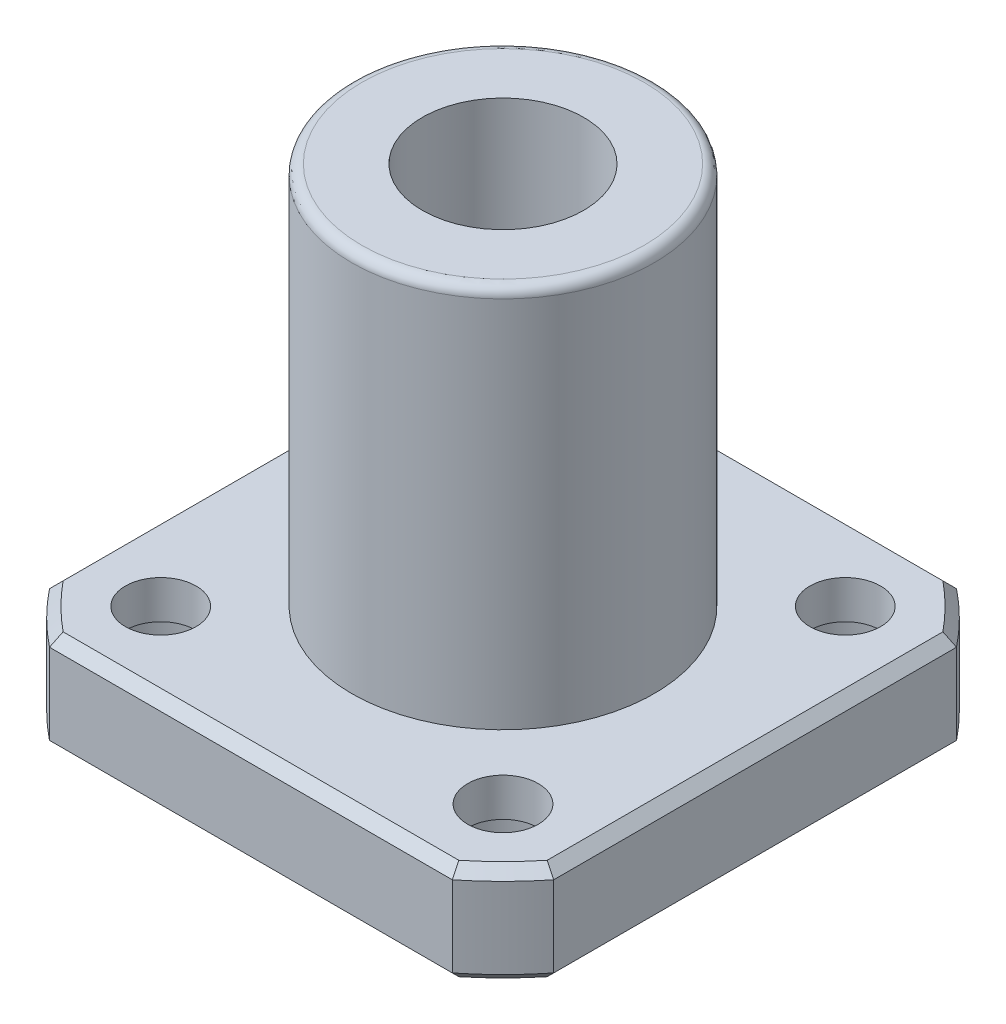
SolidWorks part; units mm, degrees
ref_plane "前视基准面" through (0, 0, 0) normal (0, 0, 1) x (1, 0, 0)
ref_plane "上视基准面" through (0, 0, 0) normal (0, 1, 0) x (1, 0, 0)
ref_plane "右视基准面" through (0, 0, 0) normal (1, 0, 0) x (0, 0, -1)
sketch "草图1" plane through (0, 0, 0) normal (0, 1, 0) x (1, 0, 0)
  line L1 (-12.5, -12.5) -> (12.5, -12.5)
  line L2 (-12.5, -12.5) -> (-12.5, 12.5)
  line L3 (-12.5, 12.5) -> (12.5, 12.5)
  line L4 (12.5, -12.5) -> (12.5, 12.5)
  line L5 (-12.5, -12.5) -> (12.5, 12.5) construction
  line L6 (-12.5, 12.5) -> (12.5, -12.5) construction
  circle A0 centre (0, 0) radius 4
  circle A1 centre (0, 0) radius 7.5
  circle A2 centre (0, 0) radius 16
  circle A3 centre (0, 0) radius 12 construction
  circle A4 centre (-8.4853, 8.4853) radius 1.75
  circle A5 centre (8.4853, 8.4853) radius 1.75
  circle A6 centre (8.4853, -8.4853) radius 1.75
  circle A7 centre (-8.4853, -8.4853) radius 1.75
  dimension "D1" = 8
  dimension "D2" = 15
  dimension "D5" = 32
  dimension "D6" = 24
  dimension "D7" = 3.5
  dimension "D3" = 25
  dimension "D4" = 25
  dimension "D8" = 4
extrude "凸台-拉伸1" add sketch "草图1" along normal blind 5 contours L1 A2 L4 L3 L2 A7 A6 A5 A4 A1 region at (-11.0637, 0, 11.0637)
extrude "凸台-拉伸2" add sketch "草图1<3>" along normal blind 24 contours A1 A0 region at (-7.2879, 0, 0)
sketch "草图1<3>" plane through (0, 0, 0) normal (0, 1, 0) x (1, 0, 0) same geometry as "草图1"
sketch "草图2" plane through (0, 0, 0) normal (0, -1, 0) x (1, 0, 0)
  circle A0 centre (-8.4853, 8.4853) radius 3
  circle A1 centre (8.4853, 8.4853) radius 3
  circle A2 centre (8.4853, -8.4853) radius 3
  circle A3 centre (-8.4853, -8.4853) radius 3
  dimension "D1" = 6
  dimension "D2" = 4
extrude "切除-拉伸1" cut sketch "草图2" against normal blind 3.1
chamfer "倒角1" distance 0.5 angle 45 8 edges at (-11.3137, 5, -11.3137) (0, 5, -12.5) (11.3137, 5, -11.3137) (12.5, 5, 0) (11.3137, 5, 11.3137) (0, 5, 12.5) (-11.3137, 5, 11.3137) (-12.5, 5, 0)
chamfer "倒角2" distance 0.5 angle 45 8 edges at (11.3137, 0, -11.3137) (0, 0, -12.5) (-11.3137, 0, -11.3137) (-12.5, 0, 0) (-11.3137, 0, 11.3137) (0, 0, 12.5) (12.5, 0, 0) (11.3137, 0, 11.3137)
fillet "圆角1" radius 0.5 1 edges at (0, 24, 7.5)
